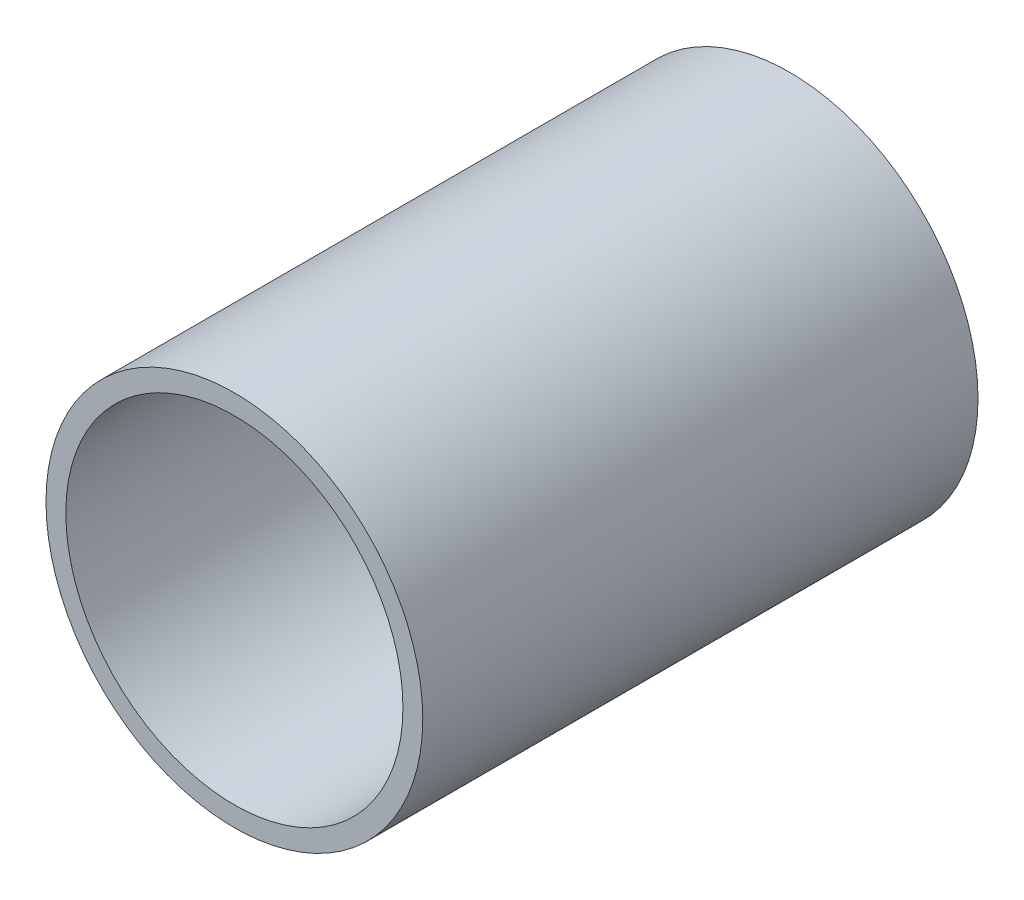
SolidWorks part; units mm, degrees
ref_plane "Front Plane" through (0, 0, 0) normal (0, 0, 1) x (1, 0, 0)
ref_plane "Top Plane" through (0, 0, 0) normal (0, 1, 0) x (1, 0, 0)
ref_plane "Right Plane" through (0, 0, 0) normal (1, 0, 0) x (0, 0, -1)
sketch "Sketch1" plane through (0, 0, 0) normal (0, 0, 1) x (1, 0, 0)
  circle A0 centre (0, 0) radius 60.325
  dimension "D1" = 120.65
extrude "Boss-Extrude1" add sketch "Sketch1" along normal blind 177.8
sketch "Sketch2" plane through (0, 0, 177.8) normal (0, 0, 1) x (1, 0, 0)
  circle A0 centre (0, 0) radius 31.75
  dimension "D1" = 63.5
extrude "Cut-Extrude1" cut sketch "Sketch2" against normal through all
sketch "Sketch3" plane through (0, 0, 177.8) normal (0, 0, 1) x (1, 0, 0)
  circle A0 centre (0, 0) radius 53.975
  dimension "D1" = 107.95
extrude "Cut-Extrude2" cut sketch "Sketch3" against normal blind 165.1
